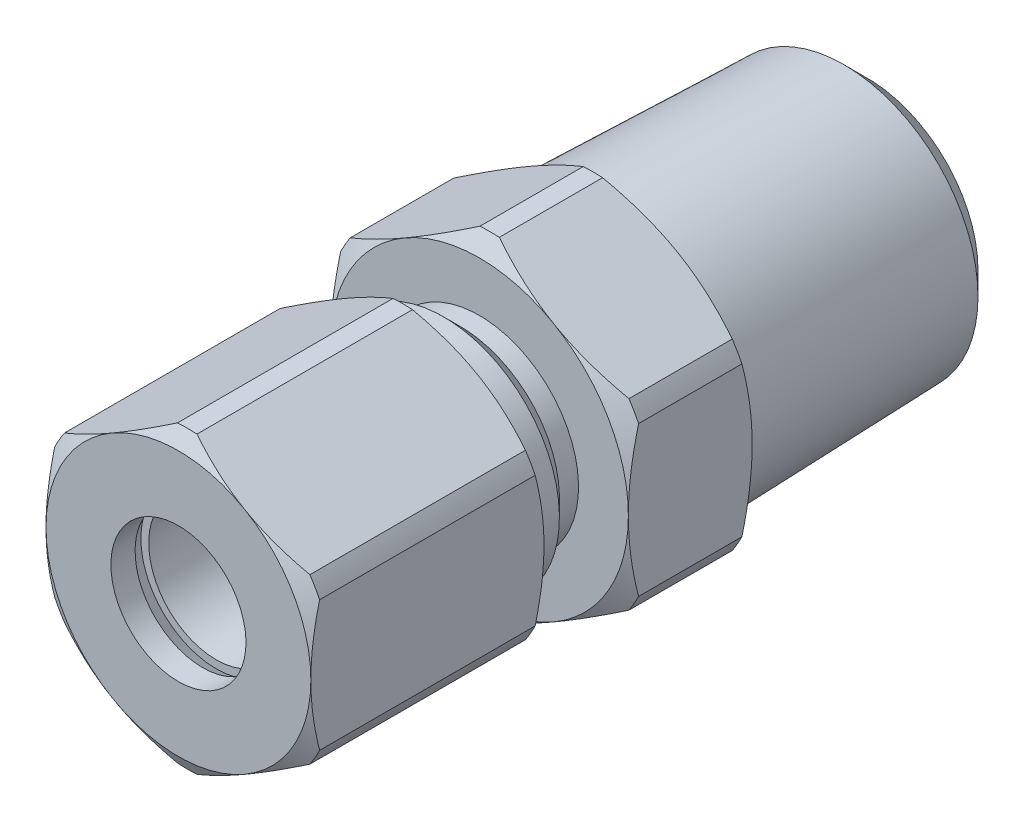
SolidWorks part; units mm, degrees
material "Brass"
ref_plane "Front Plane" through (0, 0, 0) normal (0, 0, 1) x (1, 0, 0)
ref_plane "Top Plane" through (0, 0, 0) normal (0, 1, 0) x (1, 0, 0)
ref_plane "Right Plane" through (0, 0, 0) normal (1, 0, 0) x (0, 0, -1)
sketch "Sketch1" plane through (0, 0, 0) normal (1, 0, 0) x (0, 0, -1)
  line L0 (-16.51, 0) -> (-5.334, 0) construction
  line L1 (-16.51, -6.35) -> (-16.51, 6.35) construction
  line L2 (-16.51, 3.2385) -> (-16.51, -3.2385) construction
  line L3 (-5.334, 5.5562) -> (-5.334, -5.5562) construction
  line L4 (-16.51, 3.2385) -> (-15.3494, 3.2385) construction
  line L5 (-15.3494, 3.2385) -> (-11.335, 5.5562) construction
  line L6 (-11.335, 5.5562) -> (-5.334, 5.5562) construction
  line L7 (-14.6968, 3.2385) -> (-8.3468, 3.2385) construction
  line L8 (-8.3468, 3.2385) -> (-8.3468, 3.6153) construction
  line L9 (-8.3468, 3.6153) -> (-9.652, 4.3688) construction
  line L10 (-9.652, 4.3688) -> (-13.3917, 4.3688) construction
  line L11 (-13.3917, 4.3688) -> (-14.6968, 3.6153) construction
  line L12 (-14.6968, 3.6153) -> (-14.6968, 3.2385) construction
  line L13 (-15.3494, 3.2385) -> (-14.6968, 3.2385) construction
  line L14 (-14.6968, 4.3688) -> (-14.6968, 3.992) construction
  line L15 (-14.6968, 4.3688) -> (-13.3917, 4.3688) construction
  line L16 (-14.6968, 3.992) -> (-14.6968, 3.6153) construction
  line L17 (-16.51, 0) -> (16.51, 0) construction
  line L18 (0, 2.3876) -> (0, -2.3876) construction
  line L19 (-10.414, 0) -> (16.51, 0) construction
  line L20 (0, 7.1437) -> (0, -7.1437) construction
  line L21 (-2.0796, 7.1437) -> (1.4072, 7.1437) construction
  line L22 (16.51, 6.3878) -> (16.51, -6.3878) construction
  line L23 (1.4072, 6.858) -> (1.4072, -6.858) construction
  line L24 (6.3043, 6.7055) -> (6.3043, -6.7055) construction
  line L25 (3.8557, 6.7818) -> (3.8557, -6.7818) construction
  line L26 (16.51, 6.3878) -> (1.4072, 6.858) construction
  point P27 (-3.556, 0)
  point P32 (1.4072, 0)
  point P37 (6.3043, 0)
  point P40 (3.8557, 0)
  dimension "D" = 6.477
  dimension "L" = 33.02
  dimension "Nut Hex" = 12.7
  dimension "Nut L" = 11.176
  dimension "Straight Thread OD" = 11.1125
  dimension "Straight Thread Length" = 8.3344
  dimension "Sleeve OD" = 8.7376
  dimension "Sleeve L" = 6.35
  dimension "A1" = 30
  dimension "L1" = 6.858
  dimension "Flow Dia. D" = 4.7752
  dimension "M" = 26.924
  dimension "C Hex" = 14.2875
  dimension "Insertion Depth" = 6.858
  dimension "A2" = 1.783
  dimension "L4" = 15.1028
  dimension "L2" = 10.2057
  dimension "Pipe Thread OD" = 13.716
  dimension "Pipe Thread L" = 12.6543
ref_plane "Plane1" through (0, 0, 10.414) normal (0, 0, 1) x (1, 0, 0)
sketch "Sketch2" plane through (0, 0, 10.414) normal (0, 0, 1) x (1, 0, 0)
  line L0 (0, 8.2489) -> (0, 0) construction
  line L1 (0, 8.2489) -> (-7.1438, 4.1244)
  line L2 (-7.1438, 4.1244) -> (-7.1438, -4.1244)
  line L3 (-7.1438, -4.1244) -> (0, -8.2489)
  line L4 (0, -8.2489) -> (7.1437, -4.1244)
  line L5 (7.1437, -4.1244) -> (7.1438, 4.1244)
  line L6 (7.1438, 4.1244) -> (0, 8.2489)
  circle A0 centre (0, 0) radius 7.1438 construction
extrude "Boss-Extrude1" add sketch "Sketch2" against normal up to vertex (26.924 mm away) up to point (0, 0, -16.51)
sketch "Sketch3" plane through (0, 0, 0) normal (1, 0, 0) x (0, 0, -1)
  line L0 (-10.414, 5.5562) -> (-2.0796, 5.5563)
  line L1 (-2.0796, 5.5563) -> (-2.0796, 8.2489)
  line L2 (3.8557, 6.7818) -> (3.8557, 8.2489)
  line L3 (16.51, 8.2489) -> (-10.414, 8.2489) construction
  line L5 (3.8557, 8.2489) -> (16.51, 8.2489)
  line L6 (16.51, 8.2489) -> (16.51, 6.3878)
  line L7 (16.51, 6.3878) -> (3.8557, 6.7818)
  line L9 (-2.0796, 8.2489) -> (-10.414, 8.2489)
  line L10 (-10.414, 8.2489) -> (-10.414, 5.5562)
  dimension "D2" = 8.3344
  dimension "D1" = 12.6543
revolve "Cut-Revolve1" cut sketch "Sketch3" angle 360 about L17
sketch "Sketch4" plane through (0, 0, 10.414) normal (0, 0, 1) x (1, 0, 0)
  circle A3 centre (0, 0) radius 5.5562
  circle A4 centre (0, 0) radius 5.5562
  point P3 (0, 5.5563)
  dimension "D1" = 0
curve "Helix/Spiral1" [suppressed] pitch 1.0583 height 8.2021 turns 7.75 parameters "Straight Thread Pitch"=1.0583
sketch "Sketch5" plane through (0, 0, 0) normal (1, 0, 0) x (0, 0, -1)
  line L0 (-11.4062, 5.6708) -> (-10.3479, 5.6708) construction
  line L1 (-10.3479, 5.6708) -> (-10.877, 4.7543) construction
  line L2 (-10.877, 4.7543) -> (-11.4062, 5.6708) construction
  line L3 (-11.34, 5.5563) -> (-10.414, 5.5563) construction
  line L4 (-10.9432, 4.8688) -> (-10.8109, 4.8688) construction
  line L5 (-10.877, 4.7543) -> (-10.877, 4.8688) construction
  line L6 (-10.877, 5.5563) -> (-10.877, 5.6708) construction
  line L7 (-10.9432, 4.8688) -> (-11.3731, 5.6135)
  line L8 (-11.3731, 5.6135) -> (-10.3809, 5.6135)
  line L9 (-10.3809, 5.6135) -> (-10.8109, 4.8688)
  line L10 (-10.8109, 4.8688) -> (-10.9432, 4.8688)
  line L11 (-10.877, 4.7543) -> (-10.877, -5.5562) construction
  line L12 (-10.877, -5.5562) -> (-9.8187, -5.5562) construction
  line L13 (-9.8187, -5.5562) -> (-8.7604, -5.5562) construction
  line L14 (-8.7604, -5.5562) -> (-7.702, -5.5562) construction
  line L15 (-10.414, -5.5562) -> (-2.0796, -5.5562) construction
  point P10 (-10.877, 5.6135)
  dimension "D1" = 1.0583
  dimension "D2" = 0.1323
sketch "Sketch6" plane through (0, 0, 0) normal (1, 0, 0) x (0, 0, -1)
  line L0 (-2.0796, 5.6708) -> (-3.9127, 5.6708)
  line L2 (-3.9127, 5.6708) -> (-2.9962, 4.7543)
  line L3 (-2.9962, 4.7543) -> (-2.0796, 4.7543)
  line L4 (-2.0796, 4.7543) -> (-2.0796, 5.6708)
  line L5 (-10.414, 5.6708) -> (-10.414, 4.7543)
  line L6 (-10.414, 4.7543) -> (-9.4975, 5.6708)
  line L7 (-9.4975, 5.6708) -> (-10.414, 5.6708)
  line L8 (-10.877, 4.7543) -> (-10.414, 4.7543) construction
  line L9 (-9.4975, 5.6708) -> (-3.9127, 5.6708) construction
  line L10 (-2.0796, 8.2489) -> (-2.0796, 4.1244) construction
  line L11 (-10.414, 4.7543) -> (-2.9962, 4.7543) construction
  line L12 (-11.4062, 5.6708) -> (-10.3479, 5.6708) construction
revolve "Cut-Revolve2" cut sketch "Sketch6" angle 360 about L17
sweep "Cut-Sweep1" [suppressed] cut profiles "Sketch5" path "Helix/Spiral1"
sketch "Sketch7" plane through (0, 0, 0) normal (1, 0, 0) x (0, 0, -1)
  line L0 (-2.0796, 8.2489) -> (-2.0796, 7.1437)
  line L1 (-2.0796, 7.1437) -> (-1.5882, 7.9949)
  line L2 (-1.5882, 7.9949) -> (3.3643, 7.9949)
  line L3 (3.3643, 7.9949) -> (3.8557, 7.1437)
  line L4 (3.8557, 7.1437) -> (3.8557, 8.2489)
  line L5 (3.8557, 8.2489) -> (-2.0796, 8.2489)
  line L6 (-2.0796, 7.1437) -> (0, 7.1437) construction
  line L7 (-8.3468, 3.2385) -> (-3.556, 3.2385)
  line L8 (-3.556, 3.2385) -> (-3.556, 2.3876)
  line L9 (-3.556, 2.3876) -> (16.51, 2.3876)
  line L11 (-14.6968, 4.3688) -> (-9.652, 4.3688)
  line L12 (-9.652, 0) -> (-9.652, 4.3688) construction
  line L14 (16.51, 0) -> (-9.652, 0)
  line L15 (-9.652, 4.3688) -> (-8.3468, 3.6153)
  line L16 (-8.3468, 3.6153) -> (-8.3468, 3.2385)
  line L17 (0, 0) -> (0, 7.1437) construction
  line L18 (-14.6968, 4.3688) -> (-14.6968, 0)
  line L19 (-16.51, 0) -> (-5.334, 0) construction
  line L20 (-3.556, 2.3876) -> (-9.652, 2.3876) construction
  line L21 (-14.6968, 0) -> (-9.652, 0)
  line L22 (16.51, 2.3876) -> (16.51, 0)
  dimension "D1" = 30
  dimension "D2" = 0.254
revolve "Cut-Revolve3" cut sketch "Sketch7" angle 360 about L17
sketch "Sketch8" plane through (0, 0, 0) normal (1, 0, 0) x (0, 0, -1)
  line L0 (-14.6968, 3.2385) -> (-14.6968, 3.6153)
  line L1 (-14.6968, 3.6153) -> (-13.3917, 4.3688)
  line L2 (-13.3917, 4.3688) -> (-9.652, 4.3688)
  line L3 (-9.652, 4.3688) -> (-8.3468, 3.6153)
  line L4 (-8.3468, 3.6153) -> (-8.3468, 3.2385)
  line L5 (-14.6968, 3.2385) -> (-8.3468, 3.2385) construction
  line L6 (-8.3468, 3.2385) -> (-14.6968, 3.2385)
revolve "Revolve1" add sketch "Sketch8" angle 360 about L17
ref_plane "Plane2" through (0, 0, 16.51) normal (0, 0, 1) x (1, 0, 0)
sketch "Sketch9" plane through (0, 0, 16.51) normal (0, 0, 1) x (1, 0, 0)
  line L0 (0, 7.3323) -> (0, 0) construction
  line L1 (0, 7.3323) -> (-6.35, 3.6662)
  line L2 (-6.35, 3.6662) -> (-6.35, -3.6662)
  line L3 (-6.35, -3.6662) -> (0, -7.3323)
  line L4 (0, -7.3323) -> (6.35, -3.6662)
  line L5 (6.35, -3.6662) -> (6.35, 3.6662)
  line L6 (6.35, 3.6662) -> (0, 7.3323)
  circle A0 centre (0, 0) radius 6.35 construction
extrude "Boss-Extrudex1" add sketch "Sketch9" against normal up to vertex (11.176 mm away) separate body up to point (0, 0, 5.334)
sketch "Sketch10" plane through (0, 0, 0) normal (1, 0, 0) x (0, 0, -1)
  line L0 (-16.51, 0) -> (-5.334, 0)
  line L1 (-5.334, 0) -> (-5.334, 5.5562)
  line L2 (-5.4486, 5.5563) -> (-11.335, 5.5562)
  line L3 (-11.335, 5.5562) -> (-15.3494, 3.2385)
  line L4 (-15.3494, 3.2385) -> (-16.51, 3.2385)
  line L5 (-16.51, 3.2385) -> (-16.51, 0)
  line L6 (-5.334, 7.3323) -> (-5.334, 6.35)
  line L7 (-5.334, 3.6662) -> (-5.334, 7.3323) construction
  line L8 (-5.334, 6.35) -> (-5.7545, 7.0783)
  line L9 (-5.7545, 7.0783) -> (-16.0895, 7.0783)
  line L10 (-16.0895, 7.0783) -> (-16.51, 6.35)
  line L11 (-16.51, 3.6662) -> (-16.51, 7.3323) construction
  line L12 (-16.51, 6.35) -> (-16.51, 7.3323)
  line L13 (-16.51, 7.3323) -> (-5.334, 7.3323)
  line L15 (-5.334, 6.35) -> (-16.51, 6.35) construction
  line L18 (-10.877, 5.6708) -> (-5.334, 5.6708) construction
  line L19 (-11.4062, 5.6708) -> (-10.3479, 5.6708) construction
  line L20 (-5.334, 7.3323) -> (-5.334, 3.6662) construction
  line L21 (-5.4486, 5.5563) -> (-5.334, 5.6708)
  line L22 (-5.4486, 5.5563) -> (-5.334, 5.5562) construction
  line L23 (-5.334, 5.6708) -> (-5.334, 5.5562)
  dimension "D1" = 0.254
  dimension "D2" = 30
revolve "Cut-Revolve4" cut sketch "Sketch10" angle 360 about L0
split "Split1" bodies to split 115 resulting bodies 120 121 split by face at (0, -6.7818, -3.8557)
sketch "Sketch11" plane through (0, 0, -16.51) normal (0, 0, -1) x (-1, 0, 0)
  circle A1 centre (0, 0) radius 6.3878
  circle A2 centre (0, 0) radius 6.3878
  point P0 (0, 6.3878)
  dimension "D1" = 0
curve "Helix/Spiral2" [suppressed] parameters "Pitch"=1.4111
sketch "Sketch12" plane through (0, 0, 0) normal (1, 0, 0) x (0, 0, -1)
  line L0 (16.4218, 6.5405) -> (17.8329, 6.5405) construction
  line L1 (16.4218, 6.5405) -> (17.1274, 5.3185) construction
  line L2 (17.1274, 5.3185) -> (17.8329, 6.5405) construction
  line L3 (17.0392, 5.4712) -> (17.2156, 5.4712) construction
  line L4 (16.51, 6.3878) -> (17.7447, 6.3878) construction
  line L5 (17.1274, 5.3185) -> (17.1274, 5.4712) construction
  line L6 (17.1274, 6.3878) -> (17.1274, 6.5405) construction
  line L7 (17.1274, 6.4642) -> (17.7888, 6.4642) construction
  line L8 (17.7888, 6.4642) -> (16.4218, 6.5405)
  line L9 (16.4218, 6.5405) -> (17.0392, 5.4712)
  line L10 (17.0392, 5.4712) -> (17.2156, 5.4712)
  line L11 (17.2156, 5.4712) -> (17.7888, 6.4642)
  line L12 (17.1274, 5.3185) -> (17.1274, -6.3686) construction
  line L13 (17.1274, -6.3686) -> (15.7169, -6.4125) construction
  line L14 (15.7169, -6.4125) -> (14.3065, -6.4564) construction
  line L15 (14.3065, -6.4564) -> (12.8961, -6.5003) construction
  line L16 (3.8557, -6.7818) -> (16.51, -6.3878) construction
  dimension "D1" = 1.4111
  dimension "D2" = 0.1764
sweep "Cut-Sweep2" [suppressed] cut profiles "Sketch12" path "Helix/Spiral2"
sketch "Sketch13" plane through (0, 0, -16.51) normal (0, 0, -1) x (-1, 0, 0)
  circle A0 centre (0, 0) radius 5.3185
extrude "Cut-Extrude1" cut sketch "Sketch13" against normal up to vertex (15.1028 mm away) draft 45 flip side to cut up to point (0, 0, -1.4072)
combine bodies "Combine1" operation type add bodies to combine 121 123
equation "\"D3@Helix/Spiral1\" = \"D2@Sketch3\" - \"Straight Thread Pitch@Helix/Spiral1\" * 0.125"
equation "\"D1@Sketch5\" = \"Straight Thread Pitch@Helix/Spiral1\""
equation "\"D2@Sketch5\" = \"D1@Sketch5\" / 8"
equation "\"D3@Helix/Spiral2\" = \"D1@Sketch3\" + \"Pitch@Helix/Spiral2\" * 1 /  pi "
equation "\"D1@Sketch12\" = \"Pitch@Helix/Spiral2\""
equation "\"D2@Sketch12\" = \"D1@Sketch12\" / 8"
